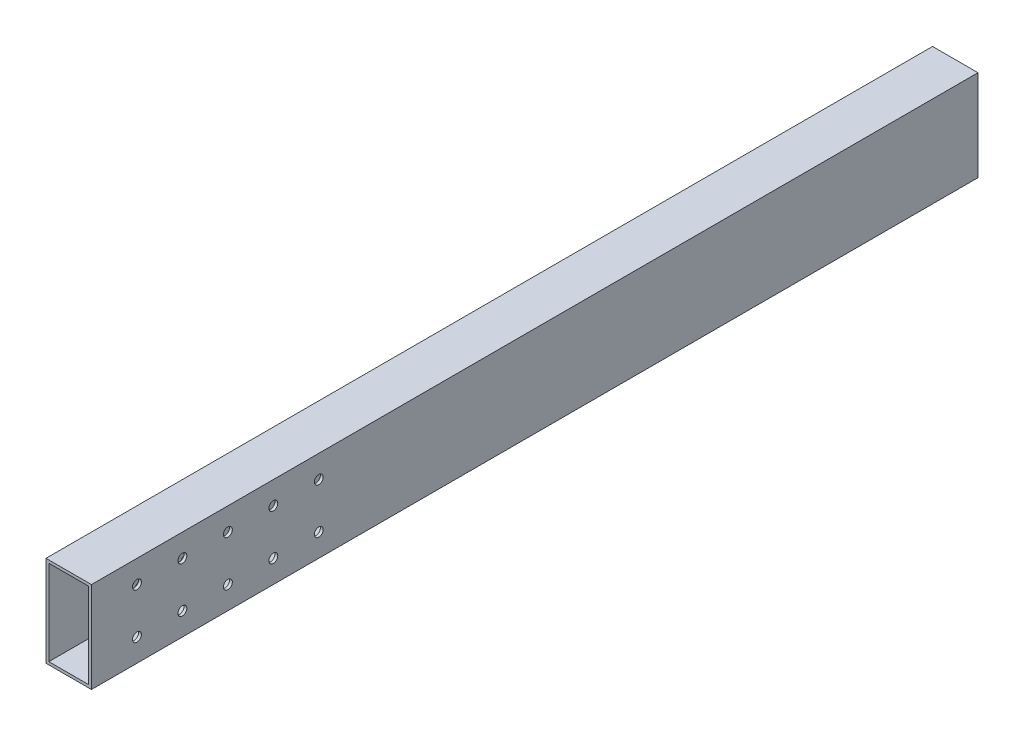
SolidWorks part; units mm, degrees
material "6061-T4 (SS)"
ref_plane "Front Plane" through (0, 0, 0) normal (0, 0, 1) x (1, 0, 0)
ref_plane "Top Plane" through (0, 0, 0) normal (0, 1, 0) x (1, 0, 0)
ref_plane "Right Plane" through (0, 0, 0) normal (1, 0, 0) x (0, 0, -1)
sketch "Sketch1" plane through (0, 0, 0) normal (0, 0, 1) x (1, 0, 0)
  line L0 (1.5875, 49.2125) -> (23.8125, 49.2125)
  line L5 (0, 0) -> (25.4, 0)
  line L6 (0, 0) -> (0, 50.8)
  line L7 (0, 50.8) -> (25.4, 50.8)
  line L8 (25.4, 0) -> (25.4, 50.8)
  line L13 (23.8125, 1.5875) -> (23.8125, 49.2125)
  line L14 (1.5875, 1.5875) -> (23.8125, 1.5875)
  line L15 (1.5875, 1.5875) -> (1.5875, 49.2125)
  dimension "D1" = 25.4
  dimension "D2" = 1.5875
  dimension "D3" = 50.8
extrude "Boss-Extrude1" add sketch "Sketch1" along normal blind 495.3
sketch "Sketch2" plane through (25.4, 0, 0) normal (-1, 0, 0) x (0, 0, 1)
  line L0 (495.3, 50.8) -> (495.3, 0) construction
  line L1 (495.3, 50.8) -> (0, 50.8) construction
  circle A16 centre (444.5, 38.1) radius 2.4892
  circle A17 centre (419.1, 38.1) radius 2.4892
  circle A18 centre (393.7, 38.1) radius 2.4892
  circle A19 centre (368.3, 38.1) radius 2.4892
  circle A21 centre (444.5, 12.7) radius 2.4892
  circle A22 centre (419.1, 12.7) radius 2.4892
  circle A23 centre (393.7, 12.7) radius 2.4892
  circle A24 centre (368.3, 12.7) radius 2.4892
  circle A26 centre (469.9, 12.7) radius 2.4892
  circle A29 centre (469.9, 38.1) radius 2.4892
  circle A30 centre (342.9, 38.1) radius 2.4892 [skipped]
  circle A31 centre (342.9, 12.7) radius 2.4892 [skipped]
  point P2 (0, 0)
  point P14 (0, 0)
  dimension "D4" = 25.4
  dimension "D5" = 6
  dimension "D6" = 2
  dimension "D1" = 4.9784
  dimension "D7" = 12.7
  dimension "D2" = 25.4
  dimension "D3" = 25.4
extrude "Cut-Extrude1" cut sketch "Sketch2" along normal up to next contours A24 | A23 | A18 | A19
sketch "Sketch3" plane through (0, 0, 0) normal (-1, 0, 0) x (0, 0, 1)
  line L0 (495.3, 25.4) -> (0, 25.4) construction
  line L1 (495.3, 50.8) -> (495.3, 0) construction
  line L2 (0, 50.8) -> (0, 0) construction
  line L4 (88.9, 41.275) -> (139.7, 41.275) construction
  line L5 (88.9, 41.275) -> (88.9, 9.525) construction
  line L6 (88.9, 9.525) -> (139.7, 9.525) construction
  line L7 (139.7, 41.275) -> (139.7, 9.525) construction
  line L8 (88.9, 41.275) -> (139.7, 9.525) construction
  line L9 (88.9, 9.525) -> (139.7, 41.275) construction
  circle A0 centre (114.3, 25.4) radius 14.2875
  circle A1 centre (139.7, 41.275) radius 2.4892
  circle A2 centre (88.9, 41.275) radius 2.4892
  circle A3 centre (88.9, 9.525) radius 2.4892
  circle A4 centre (139.7, 9.525) radius 2.4892
  dimension "D1" = 28.575
  dimension "D2" = 114.3
  dimension "D5" = 4.9784
  dimension "D3" = 15.875
  dimension "D4" = 25.4
extrude "Cut-Extrude2" cut sketch "Sketch3" against normal up to next
extrude "Cut-Extrude5" cut sketch "Sketch2<3>" along normal through all contours A22 | A17 | A26 | A29 | A16 | A21 region at (25.4, 38.1, 444.5) region at (25.4, 38.1, 419.1) region at (25.4, 12.7, 444.5) region at (25.4, 12.7, 419.1) region at (25.4, 12.7, 469.9) region at (25.4, 38.1, 469.9)
sketch "Sketch2<3>" plane through (25.4, 0, 0) normal (-1, 0, 0) x (0, 0, 1) same geometry as "Sketch2"
